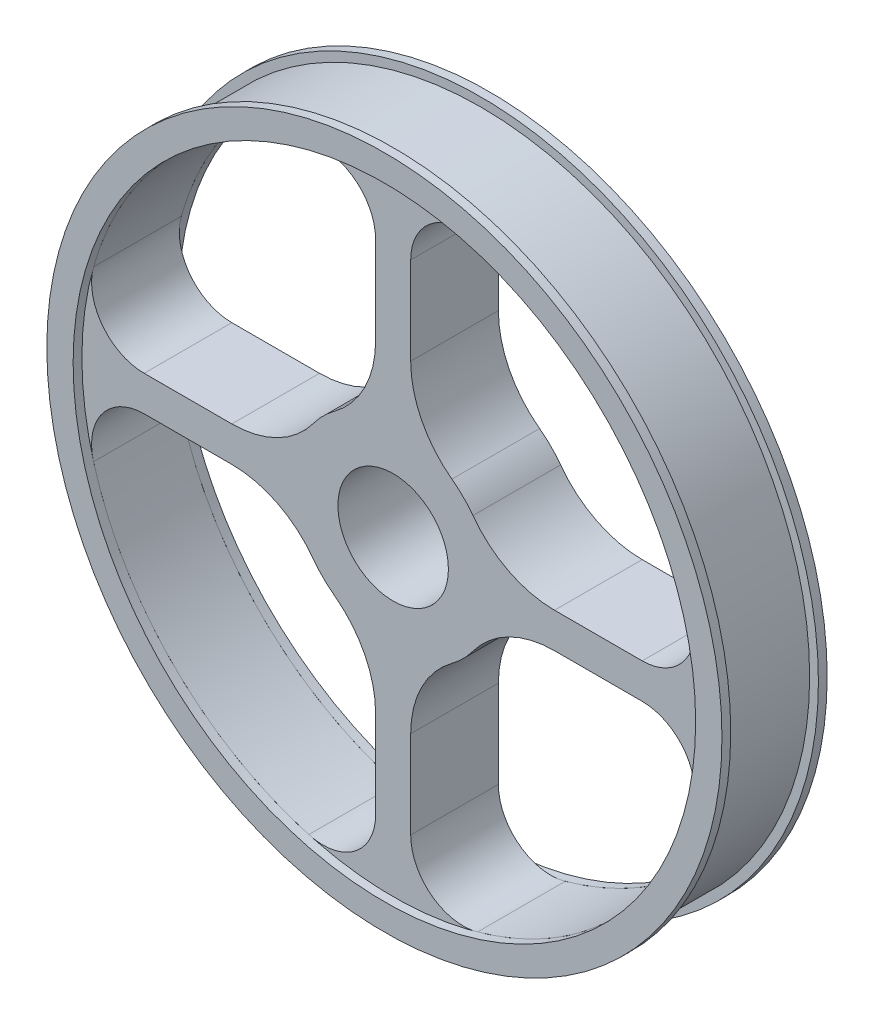
SolidWorks part; units mm, degrees
material "ABS"
ref_plane "Front Plane" through (0, 0, 0) normal (0, 0, 1) x (1, 0, 0)
ref_plane "Top Plane" through (0, 0, 0) normal (0, 1, 0) x (1, 0, 0)
ref_plane "Right Plane" through (0, 0, 0) normal (1, 0, 0) x (0, 0, -1)
sketch "Sketch1" plane through (0, 0, 0) normal (0, 0, 1) x (1, 0, 0)
  line L0 (0, 2.87) -> (0, 9.017) construction
  line L2 (0.508, 7.2135) -> (0.508, 4.6735)
  line L4 (-0.508, 7.2135) -> (-0.508, 4.6735)
  line L5 (7.2135, 0.508) -> (4.6735, 0.508)
  line L6 (0, 5.9435) -> (-0.508, 5.9435) construction
  line L7 (7.2135, -0.508) -> (4.6735, -0.508)
  line L8 (0.508, -7.2135) -> (0.508, -4.6735)
  line L9 (-0.508, -7.2135) -> (-0.508, -4.6735)
  line L10 (-7.2135, -0.508) -> (-4.6735, -0.508)
  line L11 (-7.2135, 0.508) -> (-4.6735, 0.508)
  circle A1 centre (0, 0) radius 2.87
  circle A5 centre (0, 0) radius 9.017
  circle A7 centre (0, 0) radius 9.525
  circle A8 centre (0, 0) radius 9.779
  arc A9 (-0.508, 7.2135) -> (-2.4438, 8.6795) centre (-2.031, 7.2135) ccw
  arc A10 (-0.508, 4.6735) -> (-1.7021, 2.3108) centre (-3.4425, 4.6735) cw
  arc A11 (0.508, 4.6735) -> (1.7021, 2.3108) centre (3.4425, 4.6735) ccw
  arc A12 (0.508, 7.2135) -> (2.4438, 8.6795) centre (2.031, 7.2135) cw
  arc A13 (4.6735, 0.508) -> (2.3108, 1.7021) centre (4.6735, 3.4425) cw
  arc A14 (7.2135, 0.508) -> (8.6795, 2.4438) centre (7.2135, 2.031) ccw
  arc A15 (7.2135, -0.508) -> (8.6795, -2.4438) centre (7.2135, -2.031) cw
  arc A16 (4.6735, -0.508) -> (2.3108, -1.7021) centre (4.6735, -3.4425) ccw
  arc A17 (0.508, -4.6735) -> (1.7021, -2.3108) centre (3.4425, -4.6735) cw
  arc A18 (0.508, -7.2135) -> (2.4438, -8.6795) centre (2.031, -7.2135) ccw
  arc A19 (-0.508, -7.2135) -> (-2.4438, -8.6795) centre (-2.031, -7.2135) cw
  arc A20 (-0.508, -4.6735) -> (-1.7021, -2.3108) centre (-3.4425, -4.6735) ccw
  arc A21 (-4.6735, -0.508) -> (-2.3108, -1.7021) centre (-4.6735, -3.4425) cw
  arc A22 (-7.2135, -0.508) -> (-8.6795, -2.4438) centre (-7.2135, -2.031) ccw
  arc A23 (-7.2135, 0.508) -> (-8.6795, 2.4438) centre (-7.2135, 2.031) cw
  arc A24 (-4.6735, 0.508) -> (-2.3108, 1.7021) centre (-4.6735, 3.4425) ccw
  circle A25 centre (0, 0) radius 1.6
  circle A26 centre (0, 0) radius 1.6 construction
  point P64 (0, 0)
  dimension "D1" = 1.27
  dimension "D2" = 0.508
  dimension "D3" = 19.05
  dimension "D4" = 0.254
  dimension "D5" = 0.508
  dimension "D6" = 2.54
  dimension "D7" = 4
extrude "Boss-Extrude1" add sketch "Sketch1" along normal mid plane 2.54 contours A7 A5 | L2 A12 A5 A9 L4 A10 A1 A11 | A16 L7 A15 A5 A14 L5 A13 A1 | A24 L11 A23 A5 A22 L10 A21 A1 | A20 L9 A19 A5 A18 L8 A17 A1 | A1 A25 region at (0, 6.0984, 0) region at (1.972, 1.972, 0) region at (6.0984, 0, 0) region at (-6.0984, 0, 0) region at (0, -6.0984, 0) region at (-9.2556, 0, 0)
extrude "Boss-Extrude2" add sketch "Sketch1<5>" along normal blind 0.254 from surface separate body contours A7 A5 | A8 A7 region at (-9.2556, 0, 0) region at (-9.7513, 0, 0) starting at face at (3.5712, -3.5712, 1.27)
sketch "Sketch1<5>" plane through (0, 0, 0) normal (0, 0, 1) x (1, 0, 0) same geometry as "Sketch1"
mirror "Mirror2" about plane through (0, 0, 0) normal (0, 0, 1) of bodies 105 102
